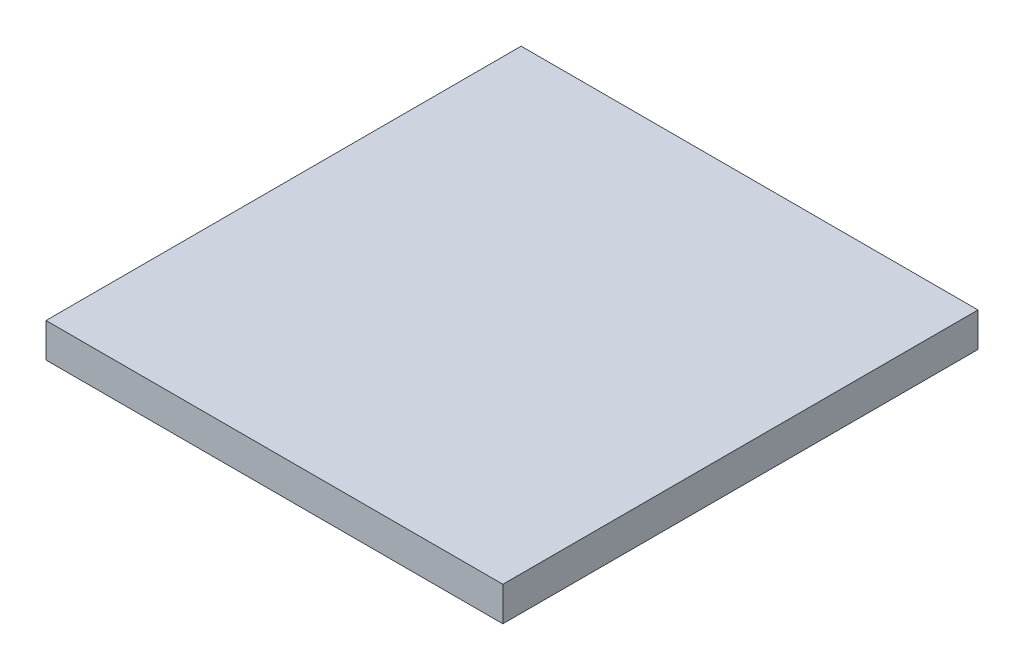
SolidWorks part; units mm, degrees
ref_plane "Front Plane" through (0, 0, 0) normal (0, 0, 1) x (1, 0, 0)
ref_plane "Top Plane" through (0, 0, 0) normal (0, 1, 0) x (1, 0, 0)
ref_plane "Right Plane" through (0, 0, 0) normal (1, 0, 0) x (0, 0, -1)
sketch "Sketch1" plane through (0, -679.7789, 0) normal (0, -1, 0) x (1, 0, 0)
  line L167 (48.2186, -154.2657) -> (48.2186, -153.9218)
  line L168 (43.4221, -151.8619) -> (43.4221, -140.5919)
  line L169 (43.4221, -140.5919) -> (18.0221, -140.5919)
  line L170 (18.0221, -140.5919) -> (18.0221, -138.0519)
  line L171 (18.0221, -138.0519) -> (68.8221, -138.0519)
  line L172 (68.8221, -138.0519) -> (68.8221, -140.5919)
  line L173 (68.8221, -140.5919) -> (43.4221, -140.5919)
  line L174 (43.4221, -140.5919) -> (43.4221, -143.1319)
  line L180 (48.2186, -142.1199) -> (48.2186, -138.0819)
  line L181 (43.4221, -143.1319) -> (47.2066, -143.1319)
  line L182 (48.2186, -138.0819) -> (52.0028, -138.0819)
  line L183 (52.8867, -138.448) -> (56.4296, -141.9909)
  line L184 (55.9147, -147.4969) -> (55.6565, -147.8656)
  line L185 (55.6565, -147.1281) -> (55.9147, -147.4969)
  line L186 (56.4296, -153.0028) -> (52.8867, -156.5458)
  line L187 (52.0028, -156.9119) -> (48.2186, -156.9119)
  line L188 (48.2186, -154.2657) -> (48.0466, -154.0937)
  line L189 (48.0466, -154.0937) -> (48.2186, -153.9218)
  line L190 (48.2186, -156.9119) -> (48.2186, -154.2657)
  line L191 (48.2186, -153.9218) -> (48.2186, -152.8739)
  line L192 (47.2066, -151.8619) -> (43.4221, -151.8619)
  line L193 (48.2186, -142.1199) -> (48.2186, -138.0819)
  line L194 (43.4221, -143.1319) -> (47.2066, -143.1319)
  line L195 (48.2186, -138.0819) -> (52.0028, -138.0819)
  line L196 (52.8867, -138.448) -> (56.4296, -141.9909)
  line L197 (55.9147, -147.4969) -> (55.6565, -147.8656)
  line L198 (55.6565, -147.1281) -> (55.9147, -147.4969)
  line L199 (56.4296, -153.0028) -> (52.8867, -156.5458)
  line L200 (52.0028, -156.9119) -> (48.2186, -156.9119)
  line L203 (48.2186, -156.9119) -> (48.2186, -154.2657)
  line L204 (48.2186, -153.9218) -> (48.2186, -152.8739)
  line L205 (47.2066, -151.8619) -> (43.4221, -151.8619)
  arc A117 (47.2066, -143.1319) -> (48.2186, -142.1199) centre (47.2066, -142.1199) ccw
  arc A118 (52.8867, -138.448) -> (52.0028, -138.0819) centre (52.0028, -139.3319) ccw
  arc A119 (56.6507, -143.4593) -> (56.4296, -141.9909) centre (55.5458, -142.8748) ccw
  arc A120 (56.6507, -143.4593) -> (55.6565, -147.1281) centre (64.2836, -147.4969) ccw
  arc A121 (55.6565, -147.8656) -> (56.6507, -151.5344) centre (64.2836, -147.4969) ccw
  arc A122 (56.4296, -153.0028) -> (56.6507, -151.5344) centre (55.5458, -152.1189) ccw
  arc A123 (52.0028, -156.9119) -> (52.8867, -156.5458) centre (52.0028, -155.6619) ccw
  arc A124 (48.2186, -152.8739) -> (47.2066, -151.8619) centre (47.2066, -152.8739) ccw
  arc A125 (47.2066, -143.1319) -> (48.2186, -142.1199) centre (47.2066, -142.1199) ccw
  arc A126 (52.8867, -138.448) -> (52.0028, -138.0819) centre (52.0028, -139.3319) ccw
  arc A127 (56.6507, -143.4593) -> (56.4296, -141.9909) centre (55.5458, -142.8748) ccw
  arc A128 (56.6507, -143.4593) -> (55.6565, -147.1281) centre (64.2836, -147.4969) ccw
  arc A129 (55.6565, -147.8656) -> (56.6507, -151.5344) centre (64.2836, -147.4969) ccw
  arc A130 (56.4296, -153.0028) -> (56.6507, -151.5344) centre (55.5458, -152.1189) ccw
  arc A131 (52.0028, -156.9119) -> (52.8867, -156.5458) centre (52.0028, -155.6619) ccw
  arc A132 (48.2186, -152.8739) -> (47.2066, -151.8619) centre (47.2066, -152.8739) ccw
  dimension "D2" = 50.8
  dimension "D3" = 2.54
  dimension "D4" = 2.54
  dimension "D1" = 0.635
extrude "Boss-Extrude1" add sketch "Sketch1" against normal blind 63.5 rebuild error yes
sketch "Sketch2" plane through (0, 0, -86.4379) normal (0, 0, 1) x (1, 0, 0)
  line L0 (56.7896, -640.3564) -> (56.7896, -703.8564) construction
  line L1 (56.7896, -700.0464) -> (107.5896, -700.0464)
  line L2 (56.7896, -700.0464) -> (56.7896, -703.8564)
  line L3 (56.7896, -703.8564) -> (107.5896, -703.8564)
  line L4 (107.5896, -700.0464) -> (107.5896, -703.8564)
  line L5 (107.5896, -640.3564) -> (107.5896, -703.8564) construction
  line L6 (107.5896, -703.8564) -> (56.7896, -703.8564) construction
  dimension "D1" = 3.81
extrude "Boss-Extrude2" add sketch "Sketch2" along normal blind 52.832
fillet "Fillet1" radius 2.54 rebuild error yes
